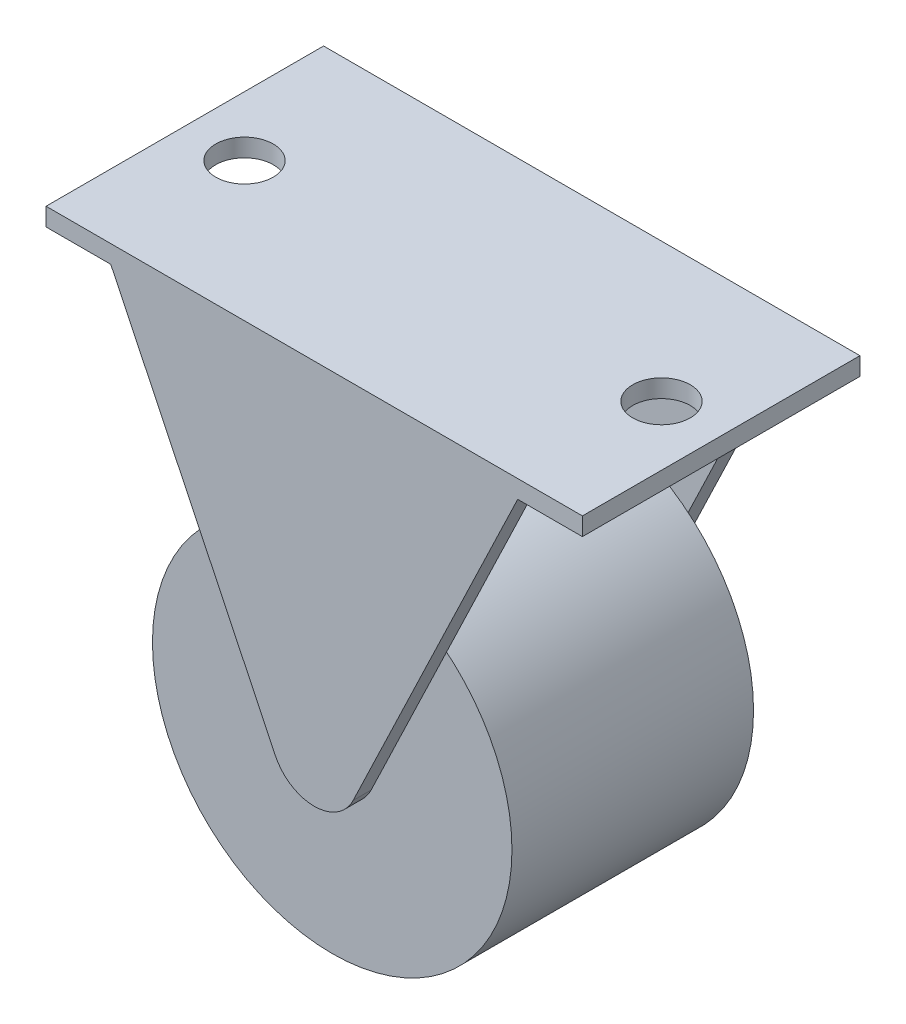
SolidWorks part; units mm, degrees
ref_plane "Front Plane" through (0, 0, 0) normal (0, 0, 1) x (1, 0, 0)
ref_plane "Top Plane" through (0, 0, 0) normal (0, 1, 0) x (1, 0, 0)
ref_plane "Right Plane" through (0, 0, 0) normal (1, 0, 0) x (0, 0, -1)
sketch "Sketch1" plane through (0, 0, 0) normal (0, 1, 0) x (1, 0, 0)
  line L0 (0, 0) -> (0, 9.65) construction
  line L1 (-18.65, 9.65) -> (18.65, 9.65)
  line L2 (-18.65, 9.65) -> (-18.65, -9.65)
  line L3 (-18.65, -9.65) -> (18.65, -9.65)
  line L4 (18.65, 9.65) -> (18.65, -9.65)
  line L5 (-12.5, 0) -> (12.5, 0) construction
  circle A0 centre (-14.5, 0) radius 2
  circle A1 centre (14.5, 0) radius 2
  point P4 (0, 9.65)
  point P6 (-18.65, 0)
  dimension "D3" = 4
  dimension "D4" = 25
  dimension "D1" = 37.3
  dimension "D2" = 19.3
extrude "Boss-Extrude1" add sketch "Sketch1" along normal blind 1.25
sketch "Sketch2" plane through (0, 0, 9.65) normal (0, 0, 1) x (1, 0, 0)
  line L0 (-14.15, 0) -> (14.15, 0)
  line L1 (-18.65, 0) -> (18.65, 0) construction
  line L2 (14.15, 0) -> (2.7049, -23.8608)
  line L3 (-2.7049, -23.8608) -> (-14.15, 0)
  arc A0 (2.7049, -23.8608) -> (-2.7049, -23.8608) centre (0, -22.5633) cw
  point P4 (0, 0)
  point P12 (0, -29.5)
  dimension "D3" = 3
  dimension "D1" = 29.5
  dimension "D2" = 4.5
extrude "Boss-Extrude2" add sketch "Sketch2" against normal blind 1.25
extrude "Boss-Extrude3" add sketch "Sketch2<2>" along normal blind 1.25 from surface starting at face at (0, 0.625, -9.65)
sketch "Sketch2<2>" plane through (0, 0, 9.65) normal (0, 0, 1) x (1, 0, 0) same geometry as "Sketch2"
sketch "Sketch3" plane through (0, 0, 8.4) normal (0, 0, -1) x (-1, 0, 0)
  circle A0 centre (0, -22.5633) radius 12.5
  arc A1 (-2.7049, -23.8608) -> (2.7049, -23.8608) centre (0, -22.5633) ccw construction
  dimension "D1" = 25
extrude "Boss-Extrude4" add sketch "Sketch3" along normal up to surface (16.8 mm away) separate body up to face at (0, -12.356, -8.4)
